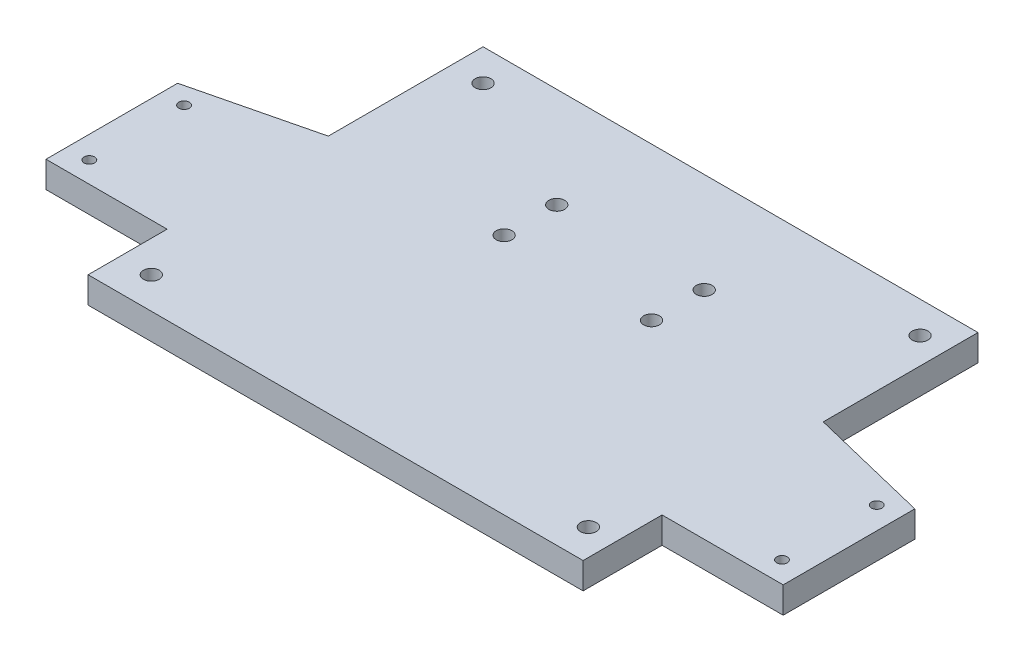
SolidWorks part; units mm, degrees
ref_plane "Front Plane" through (0, 0, 0) normal (0, 0, 1) x (1, 0, 0)
ref_plane "Top Plane" through (0, 0, 0) normal (0, 1, 0) x (1, 0, 0)
ref_plane "Right Plane" through (0, 0, 0) normal (1, 0, 0) x (0, 0, -1)
sketch "Sketch1" plane through (0, 0, 0) normal (0, 1, 0) x (1, 0, 0)
  line L24 (-28, -90) -> (-43, -105)
  line L26 (0, -90) -> (15, -105)
  line L27 (-28, -90) -> (-28, -105) construction
  line L28 (0, -90) -> (0, -105) construction
  line L32 (-28, -99) -> (0, -99) construction
  line L33 (0, -99) -> (-28, -109) construction
  line L34 (-28, -109) -> (0, -109) construction
  line L35 (0, -109) -> (-28, -99) construction
  line L36 (-28, -90) -> (0, -90)
  line L44 (-84, -115) -> (-84, -140)
  line L45 (-84, -140) -> (56, -140)
  line L46 (56, -140) -> (56, -115)
  line L48 (-84, -115) -> (-43, -105)
  line L49 (15, -105) -> (56, -115)
  line L50 (-79.77, -136) -> (-79.77, -118) construction
  line L51 (-14, -140) -> (-14, -90) construction
  circle A4 centre (-28, -99) radius 1.5
  circle A5 centre (0, -99) radius 1.5
  circle A6 centre (-28, -109) radius 1.5
  circle A7 centre (0, -109) radius 1.5
  circle A8 centre (-79.77, -136) radius 1
  circle A9 centre (-79.77, -118) radius 1
  circle A10 centre (51.77, -136) radius 1
  circle A11 centre (51.77, -118) radius 1
  dimension "D3" = 140
  dimension "D17" = 10
  dimension "D7" = 3
  dimension "D11" = 4
  dimension "D2" = 25
  dimension "D4" = 10
  dimension "D5" = 28
  dimension "D6" = 10
  dimension "D8" = 10
  dimension "D9" = 15
  dimension "D10" = 41
  dimension "D12" = 4.23
  dimension "D13" = 18
  dimension "D14" = 15
  dimension "D15" = 15
  dimension "D18" = 28
  dimension "D19" = 9
extrude "Boss-Extrude1" add sketch "Sketch1" along normal blind 3
sketch "Sketch2" plane through (0, 3, 0) normal (0, 1, 0) x (1, 0, 0)
  line L0 (56, -115) -> (15, -105) construction
  line L2 (-84, -115) -> (-84, -140)
  line L3 (-84, -140) -> (-61, -140)
  line L7 (56, -115) -> (56, -140)
  line L8 (56, -140) -> (33, -140)
  line L15 (-61, -109.3902) -> (-61, -140)
  line L16 (33, -109.3902) -> (33, -140)
  line L17 (-43, -105) -> (-84, -115) construction
  line L18 (-84, -115) -> (-61, -109.3902)
  line L19 (33, -109.3902) -> (56, -115)
  circle A0 centre (-79.77, -118) radius 1
  circle A1 centre (-79.77, -136) radius 1
  circle A2 centre (51.77, -118) radius 1
  circle A3 centre (51.77, -136) radius 1
  point P1 (33, -109.3902)
  dimension "D1" = 23
  dimension "D2" = 23
extrude "Boss-Extrude2" add sketch "Sketch2" along normal blind 2
sketch "Sketch3" plane through (0, 3, 0) normal (0, 1, 0) x (1, 0, 0)
  line L0 (-84, -115) -> (-84, -140) construction
  line L1 (-61, -155) -> (33, -155)
  line L2 (-61, -155) -> (-61, -80)
  line L3 (-61, -80) -> (-18, -80)
  line L4 (33, -155) -> (33, -80)
  line L5 (56, -140) -> (56, -115) construction
  line L6 (-61, -140) -> (33, -140) construction
  line L8 (-28, -90) -> (-43, -105) construction
  line L11 (15, -105) -> (0, -90) construction
  line L12 (-10, -80) -> (33, -80)
  line L13 (-10, -80) -> (-18, -80)
  circle A0 centre (-28, -99) radius 1.5
  circle A1 centre (0, -99) radius 1.5
  circle A2 centre (0, -109) radius 1.5
  circle A3 centre (-28, -109) radius 1.5
  dimension "D1" = 23
  dimension "D2" = 23
  dimension "D3" = 75
  dimension "D4" = 15
extrude "Boss-Extrude4" add sketch "Sketch3" along normal blind 5 from surface starting at face at (-14, 0, 112.5)
sketch "Sketch4" plane through (0, 5, 0) normal (0, 1, 0) x (1, 0, 0)
  line L0 (-61, -80) -> (-61, -109.3902) construction
  line L1 (33, -80) -> (-61, -80) construction
  line L2 (-55, -86) -> (-55, -149) construction
  line L3 (-55, -149) -> (28, -149) construction
  line L6 (28, -149) -> (28, -86) construction
  circle A0 centre (-55, -86) radius 1.5
  circle A1 centre (-55, -149) radius 1.5
  circle A2 centre (28, -149) radius 1.5
  circle A3 centre (28, -86) radius 1.5
  dimension "D1" = 6
  dimension "D4" = 83
  dimension "D2" = 6
  dimension "D3" = 63
extrude "Cut-Extrude1" cut sketch "Sketch4" against normal through all
